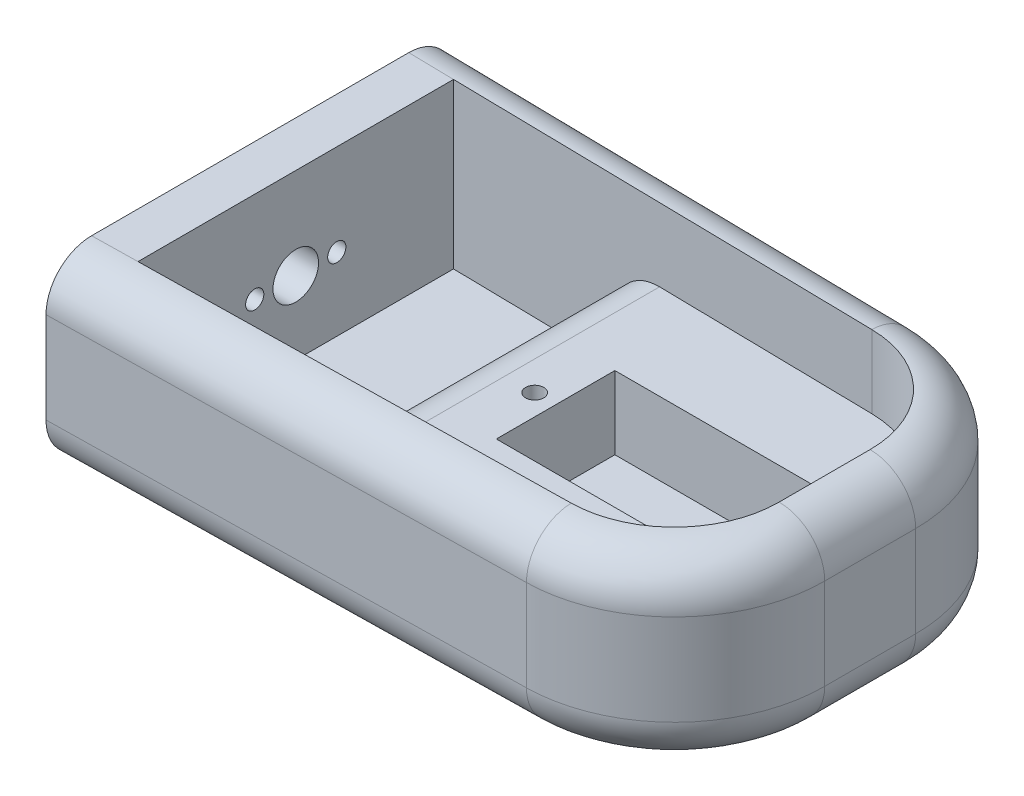
SolidWorks part; units mm, degrees
material "ABS"
ref_plane "Front Plane" through (0, 0, 0) normal (0, 0, 1) x (1, 0, 0)
ref_plane "Top Plane" through (0, 0, 0) normal (0, 1, 0) x (1, 0, 0)
ref_plane "Right Plane" through (0, 0, 0) normal (1, 0, 0) x (0, 0, -1)
sketch "Sketch2" plane through (0, 0, 0) normal (0, 1, 0) x (1, 0, 0)
  line L0 (0, 0) -> (0, 44.78)
  line L1 (0, 44.78) -> (51.788, 43.876)
  line L2 (68, 27.3786) -> (68, 17.4014)
  line L3 (51.788, 0.904) -> (0, 0)
  arc A0 (68, 17.4014) -> (51.788, 0.904) centre (51.5, 17.4014) cw
  arc A1 (51.788, 43.876) -> (68, 27.3786) centre (51.5, 27.3786) cw
  dimension "D5" = 16.5
  dimension "D1" = 89
  dimension "D2" = 89
  dimension "D3" = 44.78
  dimension "D4" = 68
extrude "Boss-Extrude1" add sketch "Sketch2" along normal blind 20
shell "Shell1" thickness 5 removed face at (41.0542, 20, -22.39)
sketch "Sketch6" plane through (0, 2, 0) normal (0, 1, 0) x (1, 0, 0)
  line L0 (23, 39.3778) -> (23, 5.4022)
  line L1 (51.7007, 38.8768) -> (5, 39.692) construction
  line L2 (5, 5.088) -> (51.7007, 5.9032) construction
  line L3 (68, 17.4014) -> (68, 27.3786) construction
  line L4 (23, 39.3778) -> (51.7007, 38.8768)
  line L7 (63, 27.3786) -> (63, 17.4014)
  line L8 (51.7007, 5.9032) -> (23, 5.4022)
  arc A0 (51.7007, 38.8768) -> (63, 27.3786) centre (51.5, 27.3786) cw
  arc A2 (51.7007, 5.9032) -> (63, 17.4014) centre (51.5, 17.4014) ccw construction
  arc A3 (63, 17.4014) -> (51.7007, 5.9032) centre (51.5, 17.4014) cw
  dimension "D1" = 45
extrude "Boss-Extrude2" add sketch "Sketch6" along normal blind 10
sketch "Sketch7" plane through (0, 12, 0) normal (0, 1, 0) x (1, 0, 0)
  line L0 (68, 17.4014) -> (68, 27.3786) construction
  line L1 (56.5, 15.89) -> (33.5, 15.89)
  line L2 (56.5, 15.89) -> (56.5, 28.89)
  line L3 (56.5, 28.89) -> (33.5, 28.89)
  line L4 (33.5, 15.89) -> (33.5, 28.89)
  dimension "D1" = 13
  dimension "D2" = 23
  dimension "D3" = 11.5
  dimension "D4" = 15.89
extrude "Cut-Extrude1" cut sketch "Sketch7" against normal blind 8
sketch "Sketch8" plane through (0, 4, 0) normal (0, 1, 0) x (1, 0, 0)
  line L0 (56.5, 15.89) -> (56.5, 28.89) construction
  line L1 (33.5, 15.89) -> (56.5, 15.89) construction
  circle A0 centre (50, 22.39) radius 6.5
  dimension "D1" = 13
  dimension "D2" = 6.5
  dimension "D3" = 6.5
extrude "Cut-Extrude2" cut sketch "Sketch8" against normal blind 8
sketch "Sketch9" plane through (0, 12, 0) normal (0, 1, 0) x (1, 0, 0)
  line L0 (33.5, 28.89) -> (33.5, 15.89) construction
  line L2 (56.5, 28.89) -> (33.5, 28.89) construction
  line L4 (56.5, 15.89) -> (56.5, 28.89) construction
  circle A0 centre (31.2, 22.39) radius 1
  circle A1 centre (58.8, 22.39) radius 1
  dimension "D1" = 2
  dimension "D2" = 2
  dimension "D3" = 2.3
  dimension "D4" = 6.5
  dimension "D5" = 6.5
  dimension "D6" = 2.3
extrude "Cut-Extrude3" cut sketch "Sketch9" against normal blind 8
sketch "Sketch10" plane through (5, 0, 0) normal (1, 0, 0) x (0, 0, -1)
  line L0 (39.692, 20) -> (5.088, 20) construction
  circle A0 centre (22.39, 10) radius 2.5
  circle A1 centre (17.89, 10) radius 1
  circle A2 centre (26.89, 10) radius 1
  dimension "D1" = 2
  dimension "D3" = 5
  dimension "D5" = 2
  dimension "D2" = 4.5
  dimension "D4" = 4.5
  dimension "D6" = 10
  dimension "D7" = 10
  dimension "D8" = 10
  dimension "D9" = 22.39
extrude "Cut-Extrude4" cut sketch "Sketch10" against normal blind 8
fillet "Fillet1" radius 5 11 edges at (25.894, 0, -0.452) (63.2686, 0, -5.8364) (68, 0, -22.39) (63.2686, 0, -38.9436) (25.894, 20, -0.452) (63.2686, 20, -5.8364) (68, 20, -22.39) (63.2686, 20, -38.9436) (23, 12, -22.39) (25.894, 0, -44.328) (25.894, 20, -44.328)
